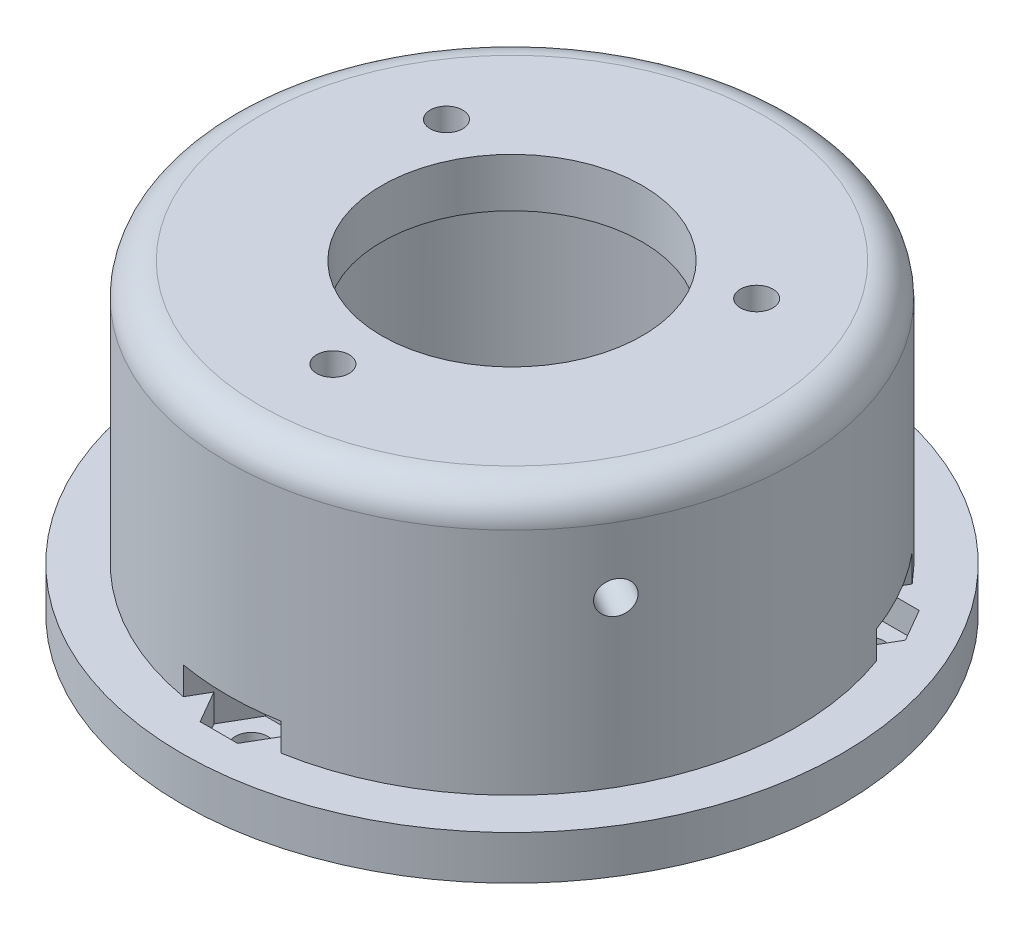
SolidWorks part; units mm, degrees
ref_plane "Front Plane" through (0, 0, 0) normal (0, 0, 1) x (1, 0, 0)
ref_plane "Top Plane" through (0, 0, 0) normal (0, 1, 0) x (1, 0, 0)
ref_plane "Right Plane" through (0, 0, 0) normal (1, 0, 0) x (0, 0, -1)
sketch "Sketch1" plane through (0, 0, 0) normal (0, 1, 0) x (1, 0, 0)
  circle A0 centre (0, 0) radius 17.45
  circle A1 centre (0, 0) radius 12.45
  dimension "D1" = 5
  dimension "D2" = 34.9
extrude "Boss-Extrude1" add sketch "Sketch1" along normal blind 8 and the other way blind 25
extrude "Boss-Extrude3" add sketch "Sketch1<2>" along normal blind 18
sketch "Sketch1<2>" plane through (0, 0, 0) normal (0, 1, 0) x (1, 0, 0) same geometry as "Sketch1"
sketch "Sketch3" plane through (0, 18, 0) normal (0, 1, 0) x (1, 0, 0)
  circle A0 centre (0, 0) radius 8
  circle A1 centre (0, 0) radius 12.45
  dimension "D1" = 16
extrude "Boss-Extrude4" add sketch "Sketch3" against normal blind 3
sketch "Sketch4" plane through (0, 18, 0) normal (0, 1, 0) x (1, 0, 0)
  line L0 (9.5263, 5.5) -> (-9.5263, 5.5) construction
  line L1 (-9.5263, 5.5) -> (0, -11) construction
  line L2 (0, -11) -> (9.5263, 5.5) construction
  circle A0 centre (0, 0) radius 11 construction
  circle A1 centre (9.5263, 5.5) radius 1
  circle A2 centre (-9.5263, 5.5) radius 1
  circle A3 centre (0, -11) radius 1
  point P14 (0, 5.5)
  dimension "D1" = 22
  dimension "D2" = 2
extrude "Cut-Extrude1" cut sketch "Sketch4" against normal blind 10
sketch "Sketch6" plane through (0, -25, 0) normal (0, -1, 0) x (1, 0, 0)
  circle A0 centre (0, 0) radius 13.5
  dimension "D1" = 27
extrude "Cut-Extrude2" cut sketch "Sketch6" against normal up to surface (40 mm away) up to face at (9.5263, 15, -4.5)
sketch "Sketch7" plane through (0, 0, 0) normal (0, 0, 1) x (1, 0, 0)
  line L0 (17.45, 18) -> (-17.45, 18) construction
  circle A0 centre (0, 12) radius 1
  dimension "D2" = 2
  dimension "D1" = 6
extrude "Cut-Extrude3" cut sketch "Sketch7" against normal blind 21
pattern_circular "CirPattern1" count 3 every 120 about axis through (0, 53.1838, 0) along (0, -1, 0) of "Cut-Extrude3"
sketch "Sketch8" plane through (0, 18, 0) normal (0, 1, 0) x (1, 0, 0)
  circle A0 centre (0, 0) radius 13.5
  circle A1 centre (0, 0) radius 20.25
  dimension "D1" = 40.5
extrude "Boss-Extrude5" add sketch "Sketch8" against normal blind 3 from offset 16.1 offset against normal yes
fillet "Fillet1" radius 2 1 edges at (0, 18, 17.45)
sketch "Sketch9" plane through (0, 0, 0) normal (1, 0, 0) x (0, 0, -1)
  line L1 (-118.0837, 0) -> (108.3743, 0)
  line L2 (-118.0837, 0) -> (-118.0837, -42.937)
  line L3 (-118.0837, -42.937) -> (108.3743, -42.937)
  line L4 (108.3743, 0) -> (108.3743, -42.937)
extrude "Cut-Extrude4" cut sketch "Sketch9" against normal blind 62 and the other way blind 34
sketch "Sketch10" plane through (0, 0, 0) normal (0, -1, 0) x (1, 0, 0)
  line L0 (13.8564, -8) -> (0, 0) construction
  line L1 (12.7017, -10) -> (15.0111, -10)
  line L2 (15.0111, -10) -> (16.1658, -8)
  line L3 (16.1658, -8) -> (15.0111, -6)
  line L4 (15.0111, -6) -> (12.7017, -6)
  line L5 (12.7017, -6) -> (11.547, -8)
  line L6 (11.547, -8) -> (12.7017, -10)
  line L7 (-15.0111, -6) -> (-16.1658, -8)
  line L8 (-16.1658, -8) -> (-15.0111, -10)
  line L9 (-15.0111, -10) -> (-12.7017, -10)
  line L10 (-12.7017, -10) -> (-11.547, -8)
  line L11 (-11.547, -8) -> (-12.7017, -6)
  line L12 (-12.7017, -6) -> (-15.0111, -6)
  line L13 (-1.1547, 18) -> (-2.3094, 16)
  line L14 (-2.3094, 16) -> (-1.1547, 14)
  line L15 (-1.1547, 14) -> (1.1547, 14)
  line L16 (1.1547, 14) -> (2.3094, 16)
  line L17 (2.3094, 16) -> (1.1547, 18)
  line L18 (1.1547, 18) -> (-1.1547, 18)
  line L19 (0, 0) -> (-13.8564, -8) construction
  line L20 (0, 0) -> (0, 16) construction
  circle A0 centre (0, 0) radius 16 construction
  circle A1 centre (13.8564, -8) radius 2 construction
  circle A2 centre (-13.8564, -8) radius 2 construction
  circle A3 centre (0, 16) radius 2 construction
  dimension "D1" = 32
  dimension "D4" = 4
  dimension "D2" = 120
  dimension "D3" = 120
extrude "Cut-Extrude5" cut sketch "Sketch10" along normal blind 1.7 and the other way blind 1.3 from surface starting at face at (0, 1.9, 17.45)
sketch "Sketch11" plane through (0, 0, 0) normal (0, -1, 0) x (1, 0, 0)
  line L0 (0, 0) -> (-13.8564, -8) construction
  line L1 (0, 0) -> (0, 16) construction
  line L2 (0, 0) -> (13.8564, -8) construction
  circle A0 centre (0, 0) radius 16 construction
  circle A1 centre (0, 16) radius 1
  circle A2 centre (13.8564, -8) radius 1
  circle A3 centre (-13.8564, -8) radius 1
  dimension "D1" = 32
  dimension "D4" = 2
  dimension "D2" = 120
  dimension "D3" = 120
extrude "Cut-Extrude6" cut sketch "Sketch11" against normal blind 3
sketch "Sketch13" plane through (0, 0, 0) normal (0, -1, 0) x (1, 0, 0)
  line L0 (13.8564, -8) -> (0, 0) construction
  line L2 (13.8564, -12) -> (17.3205, -6)
  line L4 (17.3205, -6) -> (12.7017, -6)
  line L5 (12.7017, -6) -> (11.547, -8)
  line L6 (11.547, -8) -> (13.8564, -12)
  line L8 (-17.0643, -5.6106) -> (-14.3217, -11.9728)
  line L10 (-14.3217, -11.9728) -> (-11.5627, -8.2686)
  line L11 (-11.5627, -8.2686) -> (-12.4769, -6.1479)
  line L12 (-12.4769, -6.1479) -> (-17.0643, -5.6106)
  line L14 (-3.4641, 18) -> (-1.1547, 14)
  line L15 (-1.1547, 14) -> (1.1547, 14)
  line L16 (1.1547, 14) -> (3.4641, 18)
  line L19 (0, 0) -> (-13.8564, -8) construction
  line L20 (0, 0) -> (0, 16) construction
  line L21 (2.3208, 15.9802) -> (1.1744, 17.9658) [skipped]
  line L22 (1.4889, 18) -> (-0.8039, 18) [skipped]
  line L23 (-0.9876, 18.2894) -> (-2.134, 16.3038) [skipped]
  line L24 (-3.4641, 18) -> (3.4641, 18)
  line L26 (-16.5488, -9.6983) -> (-14.2551, -9.967) [skipped]
  line L27 (-14.2694, -5.2063) -> (-15.6489, -7.0584) [skipped]
  line L28 (11.7826, -10) -> (16.3706, -10) [skipped]
  line L29 (17.7715, -10.7811) -> (15.4774, -6.8077) [skipped]
  circle A0 centre (0, 0) radius 16 construction
  circle A1 centre (13.8564, -8) radius 2 construction
  circle A2 centre (-13.8564, -8) radius 2 construction
  circle A3 centre (0, 16) radius 2 construction
  dimension "D1" = 32
  dimension "D4" = 4
  dimension "D2" = 120
  dimension "D3" = 120
extrude "Cut-Extrude7" cut sketch "Sketch13" against normal blind 1.7 from surface starting at face at (0, 1.9, 20.25)
sketch "Sketch14" plane through (0, 0, 0) normal (0, -1, 0) x (1, 0, 0)
  circle A0 centre (0, 16) radius 1
  circle A1 centre (13.8564, -8) radius 1
  circle A2 centre (-13.8564, -8) radius 1
  circle A3 centre (0, 0) radius 13.5
  circle A4 centre (0, 0) radius 20.25
  dimension "D1" = 2
extrude "Boss-Extrude6" add sketch "Sketch14" along normal blind 0.8
